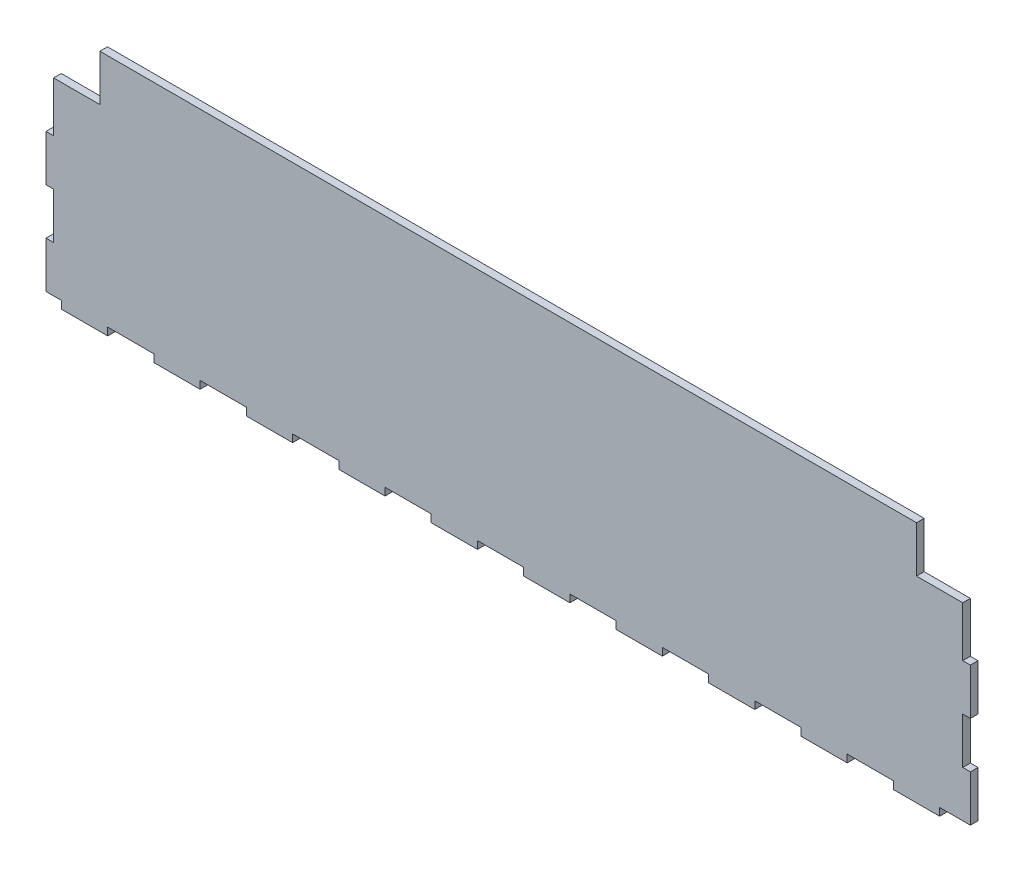
SolidWorks part; units mm, degrees
material "Balsa"
ref_plane "Front Plane" through (0, 0, 0) normal (0, 0, 1) x (1, 0, 0)
ref_plane "Top Plane" through (0, 0, 0) normal (0, 1, 0) x (1, 0, 0)
ref_plane "Right Plane" through (0, 0, 0) normal (1, 0, 0) x (0, 0, -1)
sketch "Sketch1" plane through (0, 0, 0) normal (0, 0, 1) x (1, 0, 0)
  line L0 (393.4, -121.5124) -> (393.4, -39.8043)
  line L1 (393.4, -39.8043) -> (0, -39.8043) construction
  line L2 (0, -39.8043) -> (0, -121.5124)
  line L3 (0, -121.5124) -> (393.4, -121.5124)
  line L4 (0, -138.3774) -> (0, -39.8043) construction
  line L5 (373.4, -39.8043) -> (20, -39.8043) construction
  line L6 (373.4, -39.8043) -> (373.4, -19.8043)
  line L7 (373.4, -19.8043) -> (20, -19.8043)
  line L8 (20, -39.8043) -> (20, -19.8043)
  line L9 (373.4, -39.8043) -> (20, -19.8043) construction
  line L10 (373.4, -19.8043) -> (20, -39.8043) construction
  line L13 (20.7, -19.8043) -> (372.7, -19.8043) construction
  line L14 (393.4, -39.8043) -> (393.4, -138.3812) construction
  line L19 (393.4, -39.8043) -> (373.4, -39.8043)
  line L20 (0, -39.8043) -> (20, -39.8043)
  point P2 (0, -121.5124)
  point P3 (393.4, -121.5124)
  point P12 (196.7, -29.8043)
  dimension "D1" = 20
  dimension "D2" = 20
  dimension "D3" = 20
extrude "Boss-Extrude1" add sketch "Sketch1" against normal blind 3.3 contours L2 L3 L0 L1 | L8 L1 L6 L7 region at (196.7, -71.4918, 0)
sketch "Sketch2" plane through (0, 0, 0) normal (0, 0, 1) x (1, 0, 0)
  line L0 (343.4, -121.5124) -> (323.4, -121.5124)
  line L1 (383.4, -121.5124) -> (363.4, -121.5124)
  line L2 (383.4, -121.5124) -> (383.4, -124.8124)
  line L3 (383.4, -124.8124) -> (363.4, -124.8124)
  line L4 (363.4, -121.5124) -> (363.4, -124.8124)
  line L5 (383.4, -121.5124) -> (363.4, -124.8124) construction
  line L6 (383.4, -124.8124) -> (363.4, -121.5124) construction
  line L7 (343.4, -121.5124) -> (343.4, -124.8124)
  line L8 (343.4, -124.8124) -> (323.4, -124.8124)
  line L9 (323.4, -121.5124) -> (323.4, -124.8124)
  line L10 (343.4, -121.5124) -> (323.4, -124.8124) construction
  line L11 (343.4, -124.8124) -> (323.4, -121.5124) construction
  line L12 (303.4, -121.5124) -> (283.4, -121.5124)
  line L13 (303.4, -121.5124) -> (303.4, -124.8124)
  line L14 (303.4, -124.8124) -> (283.4, -124.8124)
  line L15 (283.4, -121.5124) -> (283.4, -124.8124)
  line L16 (303.4, -121.5124) -> (283.4, -124.8124) construction
  line L17 (303.4, -124.8124) -> (283.4, -121.5124) construction
  line L18 (263.4, -121.5124) -> (243.4, -121.5124)
  line L19 (263.4, -121.5124) -> (263.4, -124.8124)
  line L20 (263.4, -124.8124) -> (243.4, -124.8124)
  line L21 (243.4, -121.5124) -> (243.4, -124.8124)
  line L22 (263.4, -121.5124) -> (243.4, -124.8124) construction
  line L23 (263.4, -124.8124) -> (243.4, -121.5124) construction
  line L24 (223.4, -121.5124) -> (203.4, -121.5124)
  line L25 (223.4, -121.5124) -> (223.4, -124.8124)
  line L26 (223.4, -124.8124) -> (203.4, -124.8124)
  line L27 (203.4, -121.5124) -> (203.4, -124.8124)
  line L28 (223.4, -121.5124) -> (203.4, -124.8124) construction
  line L29 (223.4, -124.8124) -> (203.4, -121.5124) construction
  line L30 (183.4, -121.5124) -> (163.4, -121.5124)
  line L31 (183.4, -121.5124) -> (183.4, -124.8124)
  line L32 (183.4, -124.8124) -> (163.4, -124.8124)
  line L33 (163.4, -121.5124) -> (163.4, -124.8124)
  line L34 (183.4, -121.5124) -> (163.4, -124.8124) construction
  line L35 (183.4, -124.8124) -> (163.4, -121.5124) construction
  line L36 (143.4, -121.5124) -> (123.4, -121.5124)
  line L37 (143.4, -121.5124) -> (143.4, -124.8124)
  line L38 (143.4, -124.8124) -> (123.4, -124.8124)
  line L39 (123.4, -121.5124) -> (123.4, -124.8124)
  line L40 (143.4, -121.5124) -> (123.4, -124.8124) construction
  line L41 (143.4, -124.8124) -> (123.4, -121.5124) construction
  line L42 (103.4, -121.5124) -> (83.4, -121.5124)
  line L43 (103.4, -121.5124) -> (103.4, -124.8124)
  line L44 (103.4, -124.8124) -> (83.4, -124.8124)
  line L45 (83.4, -121.5124) -> (83.4, -124.8124)
  line L46 (103.4, -121.5124) -> (83.4, -124.8124) construction
  line L47 (103.4, -124.8124) -> (83.4, -121.5124) construction
  line L48 (63.4, -121.5124) -> (43.4, -121.5124)
  line L49 (63.4, -121.5124) -> (63.4, -124.8124)
  line L50 (63.4, -124.8124) -> (43.4, -124.8124)
  line L51 (43.4, -121.5124) -> (43.4, -124.8124)
  line L52 (63.4, -121.5124) -> (43.4, -124.8124) construction
  line L53 (63.4, -124.8124) -> (43.4, -121.5124) construction
  line L54 (23.4, -121.5124) -> (3.4, -121.5124)
  line L55 (23.4, -121.5124) -> (23.4, -124.8124)
  line L56 (23.4, -124.8124) -> (3.4, -124.8124)
  line L57 (3.4, -121.5124) -> (3.4, -124.8124)
  line L58 (23.4, -121.5124) -> (3.4, -124.8124) construction
  line L59 (23.4, -124.8124) -> (3.4, -121.5124) construction
  point P4 (373.4, -123.1624)
  point P13 (333.4, -123.1624)
  point P18 (293.4, -123.1624)
  point P23 (253.4, -123.1624)
  point P28 (213.4, -123.1624)
  point P33 (173.4, -123.1624)
  point P38 (133.4, -123.1624)
  point P43 (93.4, -123.1624)
  point P48 (53.4, -123.1624)
  point P53 (13.4, -123.1624)
  dimension "D1" = 10
extrude "Boss-Extrude2" add sketch "Sketch2" against normal blind 3.3
sketch "Sketch3" plane through (0, 0, 0) normal (0, 0, 1) x (1, 0, 0)
  line L0 (396.7, -39.8043) -> (396.7, -61.5124) construction
  line L1 (393.4, -121.5124) -> (396.7, -121.5124)
  line L2 (393.4, -121.5124) -> (393.4, -101.5124)
  line L3 (393.4, -101.5124) -> (396.7, -101.5124)
  line L4 (396.7, -121.5124) -> (396.7, -101.5124)
  line L5 (393.4, -121.5124) -> (396.7, -101.5124) construction
  line L6 (393.4, -101.5124) -> (396.7, -121.5124) construction
  line L7 (393.4, -81.5124) -> (396.7, -81.5124)
  line L8 (393.4, -81.5124) -> (393.4, -61.5124)
  line L9 (393.4, -61.5124) -> (396.7, -61.5124)
  line L10 (396.7, -81.5124) -> (396.7, -61.5124)
  line L11 (393.4, -81.5124) -> (396.7, -61.5124) construction
  line L12 (393.4, -61.5124) -> (396.7, -81.5124) construction
  line L15 (-3.3, -124.4404) -> (-3.3, -121.5124) construction
  line L16 (0, -121.5124) -> (-3.3, -121.5124)
  line L17 (0, -121.5124) -> (0, -101.5124)
  line L18 (0, -101.5124) -> (-3.3, -101.5124)
  line L19 (-3.3, -121.5124) -> (-3.3, -101.5124)
  line L20 (0, -121.5124) -> (-3.3, -101.5124) construction
  line L21 (0, -101.5124) -> (-3.3, -121.5124) construction
  line L22 (0, -81.5124) -> (-3.3, -81.5124)
  line L23 (0, -81.5124) -> (0, -61.5124)
  line L24 (0, -61.5124) -> (-3.3, -61.5124)
  line L25 (-3.3, -81.5124) -> (-3.3, -61.5124)
  line L26 (0, -81.5124) -> (-3.3, -61.5124) construction
  line L27 (0, -61.5124) -> (-3.3, -81.5124) construction
  point P4 (395.05, -111.5124)
  point P14 (395.05, -71.5124)
  point P21 (-1.65, -111.5124)
  point P27 (-1.65, -71.5124)
  dimension "D1" = 20
  dimension "D3" = 20
  dimension "D2" = 2
  dimension "D4" = 2
extrude "Boss-Extrude3" add sketch "Sketch3" against normal blind 3.3
